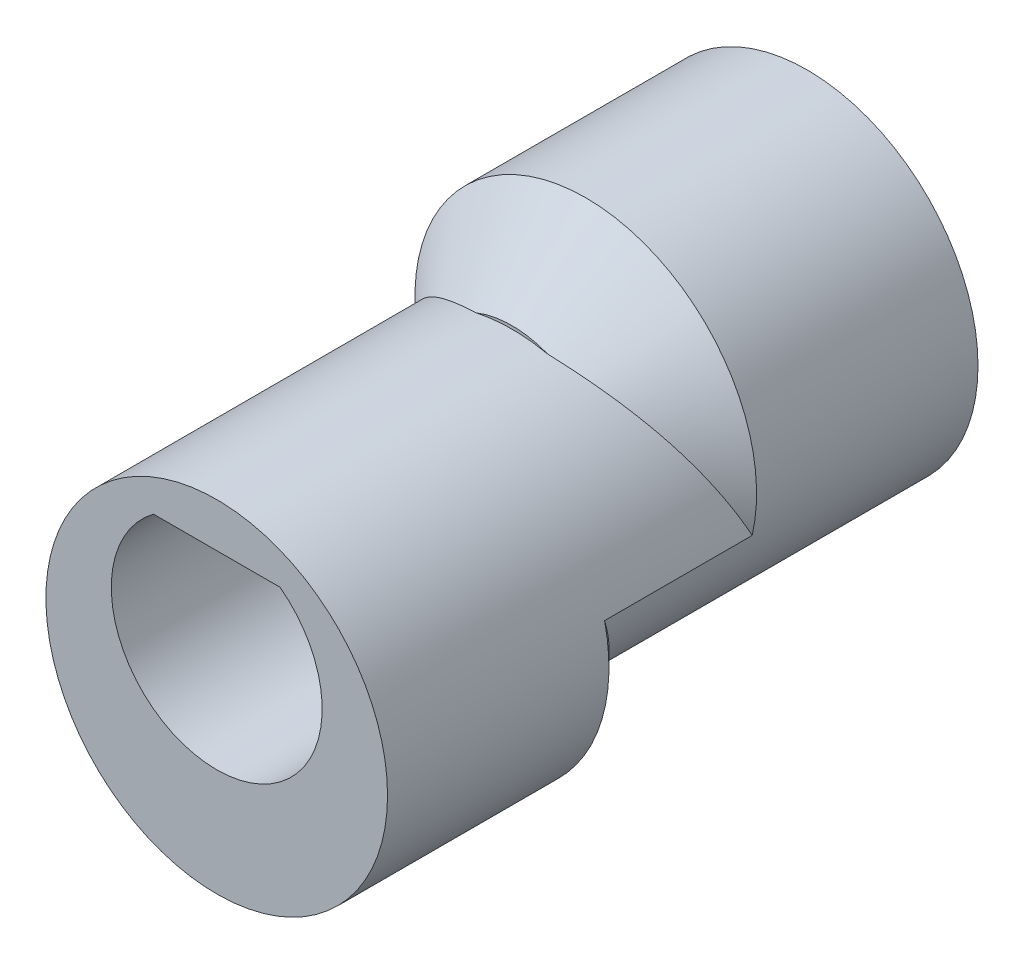
SolidWorks part; units mm, degrees
ref_plane "Plan de face" through (0, 0, 0) normal (0, 0, 1) x (1, 0, 0)
ref_plane "Plan de dessus" through (0, 0, 0) normal (0, 1, 0) x (1, 0, 0)
ref_plane "Plan de droite" through (0, 0, 0) normal (1, 0, 0) x (0, 0, -1)
sketch "Esquisse1" plane through (0, 0, 0) normal (0, 0, 1) x (1, 0, 0)
  circle A1 centre (0, 0.8221) radius 4.05
  point P7 (0, 0)
  dimension "D3" = 8.1
extrude "Boss.-Extru.1" add sketch "Esquisse1" along normal blind 7
sketch "Esquisse2" plane through (0, 0, 7) normal (0, 0, 1) x (1, 0, 0)
  circle A0 centre (0, -1) radius 4.05
  dimension "D1" = 8.1
  dimension "D2" = 1
extrude "Boss.-Extru.2" add sketch "Esquisse2" along normal blind 7
sketch "Esquisse3" plane through (0, 0, 14) normal (0, 0, 1) x (1, 0, 0)
  line L0 (-1.5, 2) -> (1.5, 2)
  arc A0 (-1.5, 2) -> (1.5, 2) centre (0, 0) ccw
  dimension "D1" = 5
  dimension "D2" = 2
extrude "Enlèv. mat.-Extru.1" cut sketch "Esquisse3" against normal through all
chamfer "Chanfrein2" distance 1.75 angle 45 1 edges at (0, 4.8721, 7)
chamfer "Chanfrein4" distance 1.75 angle 45 1 edges at (0, -5.05, 7)
